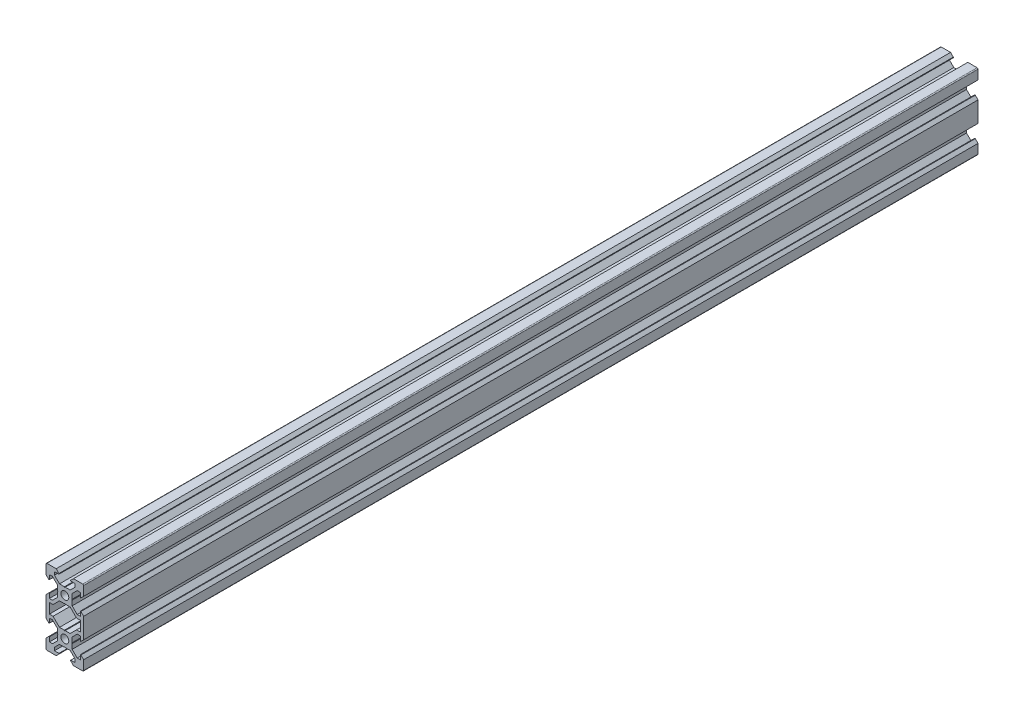
SolidWorks part; units mm, degrees
ref_plane "Plan de face" through (0, 0, 0) normal (0, 0, 1) x (1, 0, 0)
ref_plane "Plan de dessus" through (0, 0, 0) normal (0, 1, 0) x (1, 0, 0)
ref_plane "Plan de droite" through (0, 0, 0) normal (1, 0, 0) x (0, 0, -1)
ref_axis "Axe" through (0, 0, -13.782) along (0, 0, 1)
sketch "Esquisse1" plane through (0, 0, 0) normal (0, 0, 1) x (1, 0, 0)
  line L0 (0, 22.8977) -> (0, -22.8977) construction
  line L1 (-33.6074, 0) -> (33.6074, 0) construction
  line L2 (0, 0) -> (-22.2114, 22.2114) construction
  line L3 (-9.5, 10) -> (-4.58, 10)
  line L4 (-4.58, 10) -> (-3.125, 8.545)
  line L5 (-3.125, 8.545) -> (-3.125, 8.2)
  line L6 (-3.125, 8.2) -> (-5.5, 8.2)
  line L7 (-2.8393, 3.9) -> (-5.5, 6.5607)
  line L8 (-2.8393, 3.9) -> (-0.21, 3.9)
  line L9 (-5.5, 6.5607) -> (-5.5, 8.2)
  line L10 (0, 3.69) -> (0, 2.1)
  line L11 (-3.9, 2.8393) -> (-6.5607, 5.5)
  line L12 (-8.545, 3.125) -> (-8.2, 3.125)
  line L13 (-8.2, 3.125) -> (-8.2, 5.5)
  line L14 (-6.5607, 5.5) -> (-8.2, 5.5)
  line L15 (-10, 4.58) -> (-8.545, 3.125)
  line L16 (-10, 9.5) -> (-10, 4.58)
  line L17 (-0.21, 3.9) -> (0, 3.69)
  line L18 (-3.9, 2.8393) -> (-3.9, 0.21)
  line L20 (-3.9, 0.21) -> (-3.69, 0)
  line L21 (-0.21, -3.9) -> (0, -3.69)
  line L22 (0, -3.69) -> (0, -2.1)
  line L23 (-6.5607, -5.5) -> (-8.2, -5.5)
  line L24 (-2.8393, -3.9) -> (-0.21, -3.9)
  line L25 (-8.545, -3.125) -> (-8.2, -3.125)
  line L26 (-10, -4.58) -> (-8.545, -3.125)
  line L27 (-8.2, -3.125) -> (-8.2, -5.5)
  line L28 (-2.8393, -3.9) -> (-6.2393, -7.3)
  line L29 (-3.9, -2.8393) -> (-6.5607, -5.5)
  line L30 (-3.9, -2.8393) -> (-3.9, -0.21)
  line L31 (-3.9, -0.21) -> (-3.69, 0)
  line L32 (-6.2393, -7.3) -> (-8.2, -7.3)
  line L33 (-8.2, -7.3) -> (-8.2, -10)
  line L34 (-8.2, -10) -> (-10, -10)
  line L35 (-10, -10) -> (-10, -4.58)
  arc A0 (0, -2.1) -> (0, 2.1) centre (0, 0) cw
  arc A1 (-9.5, 10) -> (-10, 9.5) centre (-9.5, 9.5) ccw
  point P4 (0, 0)
  point P7 (0, 0)
  point P30 (-10, 10)
  dimension "D5" = 11
  dimension "D2" = 2.1
  dimension "D3" = 6.25
  dimension "D10" = 0.5
  dimension "D4" = 9.16
  dimension "D6" = 1.5
  dimension "D7" = 1.8
  dimension "D8" = 4.3
  dimension "D9" = 20
  dimension "D11" = 0.42
  dimension "D12" = 10
  dimension "D13" = 1.8
extrude "Boss.-Extru.1" add sketch "Esquisse1" along normal blind 475
sketch "Esquisse3" plane through (0, 0, 475) normal (0, 0, 1) x (1, 0, 0)
  line L0 (0, 0) -> (-9.8536, 9.8536) construction
  line L1 (-8.2, 8.2) -> (-8.2, 6.57)
  line L2 (-8.2, 6.57) -> (-7.54, 6.57)
  line L3 (-7.54, 6.57) -> (-6.57, 7.54)
  line L4 (-8.2, 3.125) -> (-8.2, 5.5) construction
  line L5 (-6.57, 8.2) -> (-6.57, 7.54)
  line L6 (-8.2, 8.2) -> (-6.57, 8.2)
  line L7 (-5.5, 6.5607) -> (-5.5, 8.2) construction
  arc A0 (-9.5, 10) -> (-10, 9.5) centre (-9.5, 9.5) ccw construction
  point P13 (-7.055, 7.055)
  point P14 (-6.57, 7.87)
  dimension "D1" = 1.07
extrude "Enlèv. mat.-Extru.1" [suppressed] cut sketch "Esquisse3" against normal through all
mirror "Symétrie1" about plane through (0, 3.69, 475) normal (-1, 0, 0) of "Enlèv. mat.-Extru.1", "Boss.-Extru.1"
mirror "Symétrie6" about plane through (-8.2, -10, 475) normal (0, 1, 0) of "Symétrie1", "Boss.-Extru.1"
